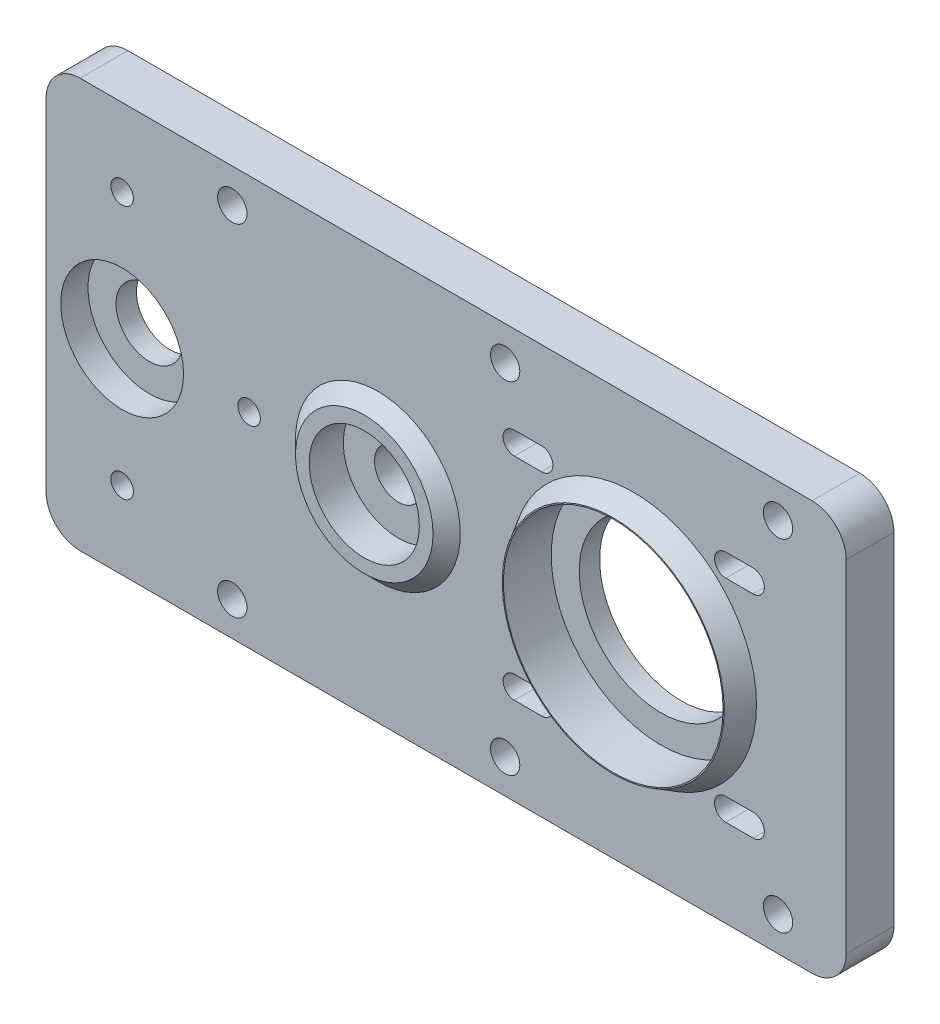
SolidWorks part; units mm, degrees
ref_plane "Front Plane" through (0, 0, 0) normal (0, 0, 1) x (1, 0, 0)
ref_plane "Top Plane" through (0, 0, 0) normal (0, 1, 0) x (1, 0, 0)
ref_plane "Right Plane" through (0, 0, 0) normal (1, 0, 0) x (0, 0, -1)
sketch "Sketch1" plane through (0, 0, 0) normal (0, 0, 1) x (1, 0, 0)
  line L0 (-27.5, 15.5) -> (-23.5, 15.5) construction
  line L1 (-25.5, 15.5) -> (5.5, 15.5) construction
  line L2 (-25.5, 15.5) -> (-25.5, -15.5) construction
  line L3 (-25.5, -15.5) -> (5.5, -15.5) construction
  line L4 (5.5, 15.5) -> (5.5, -15.5) construction
  line L5 (-25.5, 15.5) -> (5.5, -15.5) construction
  line L6 (-25.5, -15.5) -> (5.5, 15.5) construction
  line L7 (3.5, 13.85) -> (7.5, 13.85)
  line L8 (-27.5, 17.15) -> (-23.5, 17.15)
  line L9 (-27.5, 13.85) -> (-23.5, 13.85)
  line L10 (3.5, 17.15) -> (7.5, 17.15)
  line L11 (3.5, 15.5) -> (7.5, 15.5) construction
  line L12 (3.5, -17.15) -> (7.5, -17.15)
  line L13 (3.5, -13.85) -> (7.5, -13.85)
  line L14 (3.5, -15.5) -> (7.5, -15.5) construction
  line L15 (-27.5, -17.15) -> (-23.5, -17.15)
  line L16 (-27.5, -13.85) -> (-23.5, -13.85)
  line L17 (-27.5, -15.5) -> (-23.5, -15.5) construction
  line L19 (-21.15, 21.15) -> (21.15, 21.15) construction
  line L20 (-21.15, 21.15) -> (-21.15, -21.15) construction
  line L21 (-21.15, -21.15) -> (21.15, -21.15) construction
  line L22 (21.15, 21.15) -> (21.15, -21.15) construction
  line L23 (-21.15, 21.15) -> (21.15, -21.15) construction
  line L24 (-21.15, -21.15) -> (21.15, 21.15) construction
  line L29 (-78.85, 30) -> (21.15, 30)
  line L30 (-78.85, 30) -> (-78.85, -30)
  line L31 (-78.85, -30) -> (21.15, -30)
  line L32 (21.15, 30) -> (21.15, -30)
  line L33 (-78.85, 30) -> (21.15, -30) construction
  line L34 (-78.85, -30) -> (21.15, 30) construction
  arc A0 (-27.5, 17.15) -> (-27.5, 13.85) centre (-27.5, 15.5) ccw
  arc A1 (-23.5, 13.85) -> (-23.5, 17.15) centre (-23.5, 15.5) ccw
  arc A2 (3.5, 17.15) -> (3.5, 13.85) centre (3.5, 15.5) ccw
  arc A3 (7.5, 13.85) -> (7.5, 17.15) centre (7.5, 15.5) ccw
  arc A4 (3.5, -13.85) -> (3.5, -17.15) centre (3.5, -15.5) ccw
  arc A5 (7.5, -17.15) -> (7.5, -13.85) centre (7.5, -15.5) ccw
  arc A6 (-27.5, -13.85) -> (-27.5, -17.15) centre (-27.5, -15.5) ccw
  arc A7 (-23.5, -17.15) -> (-23.5, -13.85) centre (-23.5, -15.5) ccw
  circle A8 centre (-10, 0) radius 12
  point P0 (-10, 0)
  point P8 (-28.85, 0)
  point P10 (-25.5, 15.5)
  point P17 (5.5, 15.5)
  point P24 (5.5, -15.5)
  point P31 (-25.5, -15.5)
  point P39 (0, 0)
  point P44 (21.15, 0)
  dimension "D3" = 1.65
  dimension "D6" = 42.3
  dimension "D9" = 24
  dimension "D1" = 31
  dimension "D2" = 4
  dimension "D7" = 60
  dimension "D8" = 100
  dimension "D10" = 10
  dimension "D4" = 2
  dimension "D5" = 2
extrude "Boss-Extrude1" add sketch "Sketch1" along normal blind 7
sketch "Sketch2" plane through (0, 0, 7) normal (0, 0, 1) x (1, 0, 0)
  line L0 (-10, 0) -> (-22.5, 0) construction
  line L1 (-22.5, 0) -> (-47.5, 0) construction
  circle A0 centre (-10, 0) radius 12.5
  circle A1 centre (-47.5, 0) radius 25
  circle A2 centre (-10, 0) radius 12 construction
  dimension "D1" = 25
  dimension "D4" = 50
  dimension "D2" = 12.5
  dimension "D3" = 25
sketch "Sketch4" plane through (0, 0, 7) normal (0, 0, 1) x (1, 0, 0)
  circle A0 centre (-47.5, 0) radius 8.075
  dimension "D1" = 16.15
extrude "Cut-Extrude1" cut sketch "Sketch4" against normal blind 3
sketch "Sketch5" plane through (0, 0, 4) normal (0, 0, 1) x (1, 0, 0)
  circle A0 centre (-47.5, 0) radius 3.5
  dimension "D1" = 7
extrude "Cut-Extrude2" cut sketch "Sketch5" against normal blind 5
sketch "Sketch6" plane through (0, 0, 7) normal (0, 0, 1) x (1, 0, 0)
  circle A0 centre (-47.5, 0) radius 8.075
  dimension "D1" = 16.15
extrude "Extrude-Thin1" add sketch "Sketch6" along normal blind 2 thin thin type one direction wall 2
chamfer "Chamfer1" distance 2 angle 45 1 edges at (-37.425, 0, 7)
sketch "Sketch7" plane through (0, 0, 7) normal (0, 0, 1) x (1, 0, 0)
  line L0 (-78.85, 0) -> (21.15, 0) construction
  line L3 (-78.85, 30) -> (-78.85, -30) construction
  line L4 (21.15, -30) -> (21.15, 30) construction
  line L6 (-68.85, 25) -> (11.15, 25) construction
  line L7 (-68.85, 25) -> (-68.85, -25) construction
  line L8 (-68.85, -25) -> (11.15, -25) construction
  line L9 (11.15, 25) -> (11.15, -25) construction
  line L10 (-68.85, 25) -> (11.15, -25) construction
  line L11 (-68.85, -25) -> (11.15, 25) construction
  circle A0 centre (-68.85, 25) radius 2.15
  circle A1 centre (-28.85, 25) radius 2.15
  circle A2 centre (11.15, 25) radius 2.15
  circle A3 centre (11.15, -25) radius 2.15
  circle A4 centre (-28.85, -25) radius 2.15
  circle A5 centre (-68.85, -25) radius 2.15
  point P6 (-28.85, 0)
  dimension "D4" = 4.3
  dimension "D5" = 4.3
  dimension "D6" = 4.3
  dimension "D7" = 4.3
  dimension "D8" = 4.3
  dimension "D9" = 4.3
  dimension "D1" = 100
  dimension "D2" = 50
  dimension "D3" = 80
extrude "Cut-Extrude3" cut sketch "Sketch7" against normal through all
fillet "Fillet1" radius 5 4 edges at (21.15, -30, 3.5) (-78.85, -30, 3.5) (-78.85, 30, 3.5) (21.15, 30, 3.5)
sketch "Sketch8" plane through (0, 0, 0) normal (0, 0, -1) x (-1, 0, 0)
  line L1 (-9.2736, 28.25) -> (-13.0264, 28.25)
  line L2 (-13.0264, 28.25) -> (-14.9028, 25)
  line L3 (-14.9028, 25) -> (-13.0264, 21.75)
  line L4 (-13.0264, 21.75) -> (-9.2736, 21.75)
  line L5 (-9.2736, 21.75) -> (-7.3972, 25)
  line L6 (-7.3972, 25) -> (-9.2736, 28.25)
  line L7 (26.9736, 21.75) -> (30.7264, 21.75)
  line L8 (30.7264, 21.75) -> (32.6028, 25)
  line L9 (32.6028, 25) -> (30.7264, 28.25)
  line L10 (30.7264, 28.25) -> (26.9736, 28.25)
  line L11 (26.9736, 28.25) -> (25.0972, 25)
  line L12 (25.0972, 25) -> (26.9736, 21.75)
  line L13 (70.7264, 21.75) -> (72.6028, 25)
  line L14 (72.6028, 25) -> (70.7264, 28.25)
  line L15 (70.7264, 28.25) -> (66.9736, 28.25)
  line L16 (66.9736, 28.25) -> (65.0972, 25)
  line L17 (65.0972, 25) -> (66.9736, 21.75)
  line L18 (66.9736, 21.75) -> (70.7264, 21.75)
  line L19 (66.9736, -28.25) -> (70.7264, -28.25)
  line L20 (70.7264, -28.25) -> (72.6028, -25)
  line L21 (72.6028, -25) -> (70.7264, -21.75)
  line L22 (70.7264, -21.75) -> (66.9736, -21.75)
  line L23 (66.9736, -21.75) -> (65.0972, -25)
  line L24 (65.0972, -25) -> (66.9736, -28.25)
  line L25 (32.6028, -25) -> (30.7264, -21.75)
  line L26 (30.7264, -21.75) -> (26.9736, -21.75)
  line L27 (26.9736, -21.75) -> (25.0972, -25)
  line L28 (25.0972, -25) -> (26.9736, -28.25)
  line L29 (26.9736, -28.25) -> (30.7264, -28.25)
  line L30 (30.7264, -28.25) -> (32.6028, -25)
  line L31 (-7.3972, -25) -> (-9.2736, -21.75)
  line L32 (-9.2736, -21.75) -> (-13.0264, -21.75)
  line L33 (-13.0264, -21.75) -> (-14.9028, -25)
  line L34 (-14.9028, -25) -> (-13.0264, -28.25)
  line L35 (-13.0264, -28.25) -> (-9.2736, -28.25)
  line L36 (-9.2736, -28.25) -> (-7.3972, -25)
  circle A0 centre (-11.15, 25) radius 3.25 construction
  circle A1 centre (28.85, 25) radius 3.25 construction
  circle A2 centre (68.85, 25) radius 3.25 construction
  circle A3 centre (68.85, -25) radius 3.25 construction
  circle A4 centre (28.85, -25) radius 3.25 construction
  circle A5 centre (-11.15, -25) radius 3.25 construction
  dimension "D2" = 6.5
  dimension "D1" = 6.5
  dimension "D3" = 6.5
  dimension "D4" = 6.5
  dimension "D5" = 6.5
  dimension "D6" = 6.5
extrude "Cut-Extrude4" cut sketch "Sketch8" against normal blind 3
sketch "Sketch9" plane through (0, 0, 7) normal (0, 0, 1) x (1, 0, 0)
  circle A0 centre (-10, 0) radius 16.1
  dimension "D1" = 32.2
extrude "Cut-Extrude5" cut sketch "Sketch9" against normal blind 4
sketch "Sketch10" plane through (0, 0, 7) normal (0, 0, 1) x (1, 0, 0)
  circle A0 centre (-10, 0) radius 16.1
  circle A1 centre (-10, 0) radius 18
  dimension "D1" = 32.2
  dimension "D2" = 36
extrude "Boss-Extrude2" add sketch "Sketch10" along normal blind 3
chamfer "Chamfer2" distance 3 angle 30 1 edges at (8, 0, 10) first distance on face at (8, 0, 10)
sketch "Sketch11" plane through (0, 0, 0) normal (0, 0, -1) x (-1, 0, 0)
  line L0 (47.5, 0) -> (85, 0) construction
  line L1 (73.85, -30) -> (-16.15, -30) construction
  line L2 (73.85, 30) -> (96.15, 30)
  line L3 (73.85, 30) -> (73.85, -30)
  line L4 (73.85, -30) -> (96.15, -30)
  line L5 (96.15, 30) -> (96.15, -30)
  line L6 (73.85, 30) -> (96.15, -30) construction
  line L7 (73.85, -30) -> (96.15, 30) construction
  circle A0 centre (85, 0) radius 4.9
  dimension "D2" = 9.8
  dimension "D1" = 37.5
extrude "Boss-Extrude3" add sketch "Sketch11" against normal up to surface (7 mm away) up to face at (-25.5, -15.5, 7)
fillet "Fillet2" radius 5 2 edges at (-96.15, -30, 3.5) (-96.15, 30, 3.5)
sketch "Sketch12" plane through (0, 0, 7) normal (0, 0, 1) x (1, 0, 0)
  circle A0 centre (-85, 0) radius 9
  dimension "D1" = 18
extrude "Cut-Extrude6" cut sketch "Sketch12" against normal blind 4
sketch "Sketch15" plane through (0, 0, 0) normal (0, 0, -1) x (-1, 0, 0)
  circle A0 centre (85, 0) radius 18.61 construction
  circle A1 centre (85, 18.61) radius 1.65
  circle A3 centre (85, -18.61) radius 1.65
  circle A4 centre (66.39, 0) radius 1.65
  circle A5 centre (103.61, 0) radius 1.65 [skipped]
  point P8 (0, 0)
  point P9 (0, 0)
  point P17 (85, 0)
  dimension "D1" = 37.22
  dimension "D2" = 3.3
  dimension "D3" = 4
extrude "Cut-Extrude7" cut sketch "Sketch15" against normal blind 10
